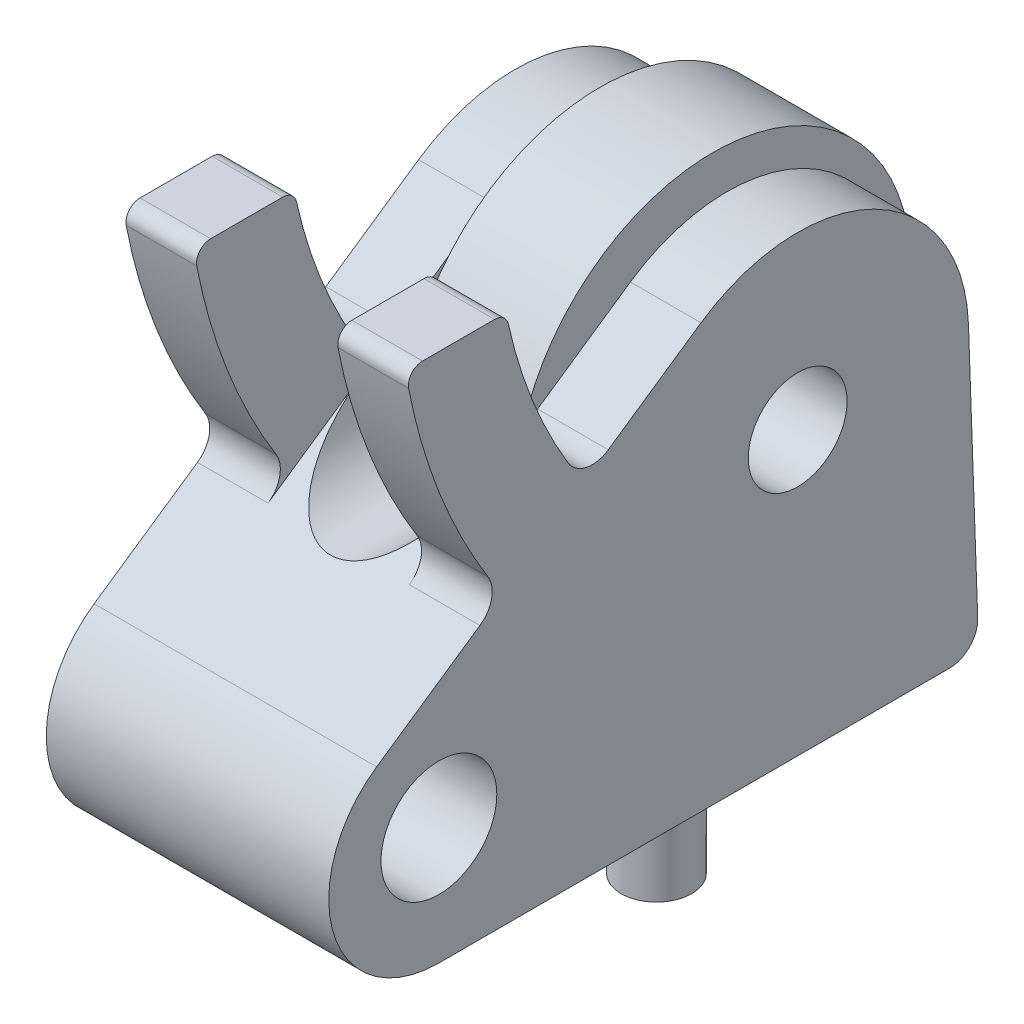
SolidWorks part; units mm, degrees
ref_plane "Спереди" through (0, 0, 0) normal (0, 0, 1) x (1, 0, 0)
ref_plane "Сверху" through (0, 0, 0) normal (0, 1, 0) x (1, 0, 0)
ref_plane "Справа" through (0, 0, 0) normal (1, 0, 0) x (0, 0, -1)
other "Configuration Table"
sketch "Sketch2" plane through (0, 0, 0) normal (1, 0, 0) x (0, 0, -1)
  line L1 (4.8077, 11.9245) -> (4.8077, 2.1)
  line L2 (0, 0) -> (18.0749, 0)
  line L3 (19.0743, 1.0357) -> (19.0363, 2.1)
  line L4 (4.8077, 2.1) -> (19.0363, 2.1)
  line L6 (-2.2052, 7.1167) -> (4.8077, 11.9245)
  circle A0 centre (0, 4.15) radius 2.05
  arc A1 (-2.2052, 7.1167) -> (0, 0) centre (0, 3.9) ccw
  arc A3 (18.0749, 0) -> (19.0743, 1.0357) centre (18.0749, 1) ccw
extrude "Boss-Extrude3" add sketch "Sketch2" along normal blind 5 and the other way blind 5
sketch "Sketch1" plane through (0, 0, 0) normal (1, 0, 0) x (0, 0, -1)
  line L0 (0, 0) -> (18.0749, 0)
  line L1 (1.9719, 18.7462) -> (-0.5804, 18.7462)
  line L2 (-2.2052, 7.1167) -> (1.4517, 9.6238)
  line L3 (5.9942, 12.738) -> (9.279, 14.9899)
  line L4 (18.7461, 10.2161) -> (19.0743, 1.0357)
  circle A0 centre (0, 4.15) radius 2.05
  arc A2 (0, 0) -> (-2.2052, 7.1167) centre (0, 3.9) cw
  circle A3 centre (12.7, 10) radius 1.75
  arc A4 (18.7461, 10.2161) -> (9.279, 14.9899) centre (12.7, 10) ccw
  arc A5 (19.0743, 1.0357) -> (18.0749, 0) centre (18.0749, 1) cw
  circle A6 centre (12.7, 10) radius 6.05 construction
  arc A7 (4.5715, 13.0478) -> (2.4602, 18.3536) centre (19.7229, 22.1499) cw
  arc A8 (1.7357, 10.9762) -> (-1.0714, 18.1518) centre (19.7229, 22.1499) cw
  arc A9 (2.2579, 10.1765) -> (-1.056, 18.0722) centre (19.7229, 22.1499) cw construction
  arc A10 (5.1447, 12.1555) -> (2.3785, 18.7462) centre (19.7229, 22.1499) cw construction
  arc A11 (5.9942, 12.738) -> (4.5715, 13.0478) centre (5.4288, 13.5627) cw
  arc A12 (1.7357, 10.9762) -> (1.4517, 9.6238) centre (0.8863, 10.4486) cw
  arc A13 (2.4602, 18.3536) -> (1.9719, 18.7462) centre (1.9719, 18.2462) ccw
  arc A14 (-1.0714, 18.1518) -> (-0.5804, 18.7462) centre (-0.5804, 18.2462) cw
  point P3 (18.75, 10)
  point P26 (5.1447, 12.1555)
  dimension "D1" = 4.3
  dimension "D2" = 1
  dimension "D4" = 1
  dimension "D5" = 0.5
  dimension "D3" = 3.5
extrude "Boss-Extrude1" add sketch "Sketch1" along normal blind 2.5 from offset 2.5
mirror "Mirror2" about plane through (0, 0, 0) normal (1, 0, 0) of "Boss-Extrude1"
sketch "Sketch4" plane through (0, 0, 0) normal (0, 0, 1) x (1, 0, 0)
  circle A0 centre (0, 11.9245) radius 2.5
extrude "Cut-Extrude1" cut sketch "Sketch4" against normal blind 21
sketch "Sketch6" plane through (0, 0, 0) normal (0, -1, 0) x (1, 0, 0)
  circle A0 centre (0, -12.7) radius 1.7
extrude "Boss-Extrude4" add sketch "Sketch6" along normal blind 2.9
sketch "Sketch7" plane through (0, -2.9, 0) normal (0, -1, 0) x (1, 0, 0)
  circle A0 centre (0, -12.7) radius 1.25
extrude "Boss-Extrude5" add sketch "Sketch7" along normal blind 3.2
sketch "Sketch8" plane through (0, 0, 0) normal (1, 0, 0) x (0, 0, -1)
  circle A0 centre (12.7, 10) radius 7
extrude "Boss-Extrude6" add sketch "Sketch8" along normal blind 2 and the other way blind 2 separate body
